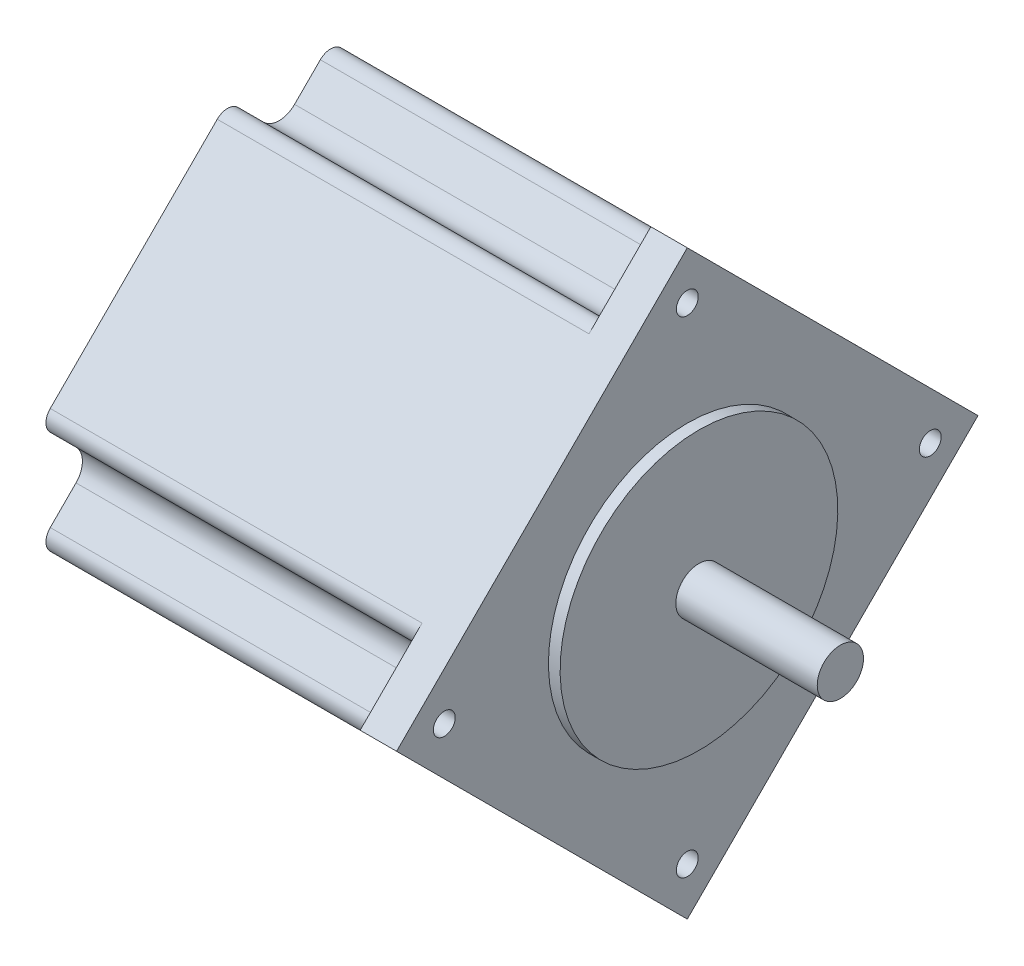
SolidWorks part; units mm, degrees
ref_plane "Plan de face" through (0, 0, 0) normal (0, 0, 1) x (1, 0, 0)
ref_plane "Plan de dessus" through (0, 0, 0) normal (0, 1, 0) x (1, 0, 0)
ref_plane "Plan de droite" through (0, 0, 0) normal (1, 0, 0) x (0, 0, -1)
ref_plane "Plan1" through (0, 607.4878, 607.4879) normal (0, 0.7071, 0.7071) x (-1, 0, 0)
sketch "Esquisse1" plane through (0, 607.4878, 607.4879) normal (0, 0.7071, 0.7071) x (-1, 0, 0)
  line L0 (138.3099, -364.0087) -> (138.3099, -307.6087)
  line L1 (138.3099, -307.6087) -> (82.3099, -307.6087)
  line L2 (82.3099, -307.6087) -> (82.3099, -364.0087)
  line L3 (82.3099, -364.0087) -> (138.3099, -364.0087)
  dimension "D1" = 56
  dimension "D2" = 56.4
extrude "Boss.-Extru.1" add sketch "Esquisse1" against normal blind 56.4
sketch "Esquisse2" plane through (0, 257.3931, -257.393) normal (0, 0.7071, -0.7071) x (-1, 0, 0)
  line L0 (138.31, 859.1175) -> (87.31, 859.1175)
  line L1 (87.31, 859.1175) -> (87.31, 849.1175)
  line L2 (87.31, 849.1175) -> (138.31, 849.1175)
  line L3 (138.31, 849.1175) -> (138.31, 859.1175)
  line L7 (82.31, 802.7175) -> (82.31, 859.1175) construction
  dimension "D1" = 5
  dimension "D2" = 10
extrude "Enlèv. mat.-Extru.1" cut sketch "Esquisse2" against normal blind 10
sketch "Esquisse3" plane through (0, 607.4878, 607.4879) normal (0, 0.7071, 0.7071) x (1, 0, 0)
  line L0 (-87.31, 307.6087) -> (-87.31, 317.6087)
  line L1 (-87.31, 317.6087) -> (-138.31, 317.6087)
  line L2 (-138.31, 317.6087) -> (-138.31, 307.6087)
  line L3 (-138.31, 307.6087) -> (-87.31, 307.6087)
  line L4 (-82.31, 307.6087) -> (-82.31, 364.0087) construction
  dimension "D1" = 10
  dimension "D2" = 5
extrude "Enlèv. mat.-Extru.2" cut sketch "Esquisse3" against normal blind 10
sketch "Esquisse4" plane through (0, 217.5122, -217.5122) normal (0, -0.7071, 0.7071) x (1, 0, 0)
  line L0 (-138.31, 802.7175) -> (-87.31, 802.7175)
  line L1 (-87.31, 802.7175) -> (-87.31, 812.7175)
  line L2 (-87.31, 812.7175) -> (-138.31, 812.7175)
  line L3 (-138.31, 812.7175) -> (-138.31, 802.7175)
  line L4 (-82.31, 802.7175) -> (-82.31, 859.1175) construction
  dimension "D1" = 10
  dimension "D2" = 5
extrude "Enlèv. mat.-Extru.3" cut sketch "Esquisse4" against normal blind 10
sketch "Esquisse5" plane through (0, 257.3931, -257.393) normal (0, 0.7071, -0.7071) x (-1, 0, 0)
  line L0 (87.31, 812.7175) -> (87.31, 802.7175)
  line L1 (87.31, 802.7175) -> (138.31, 802.7175)
  line L2 (138.31, 802.7175) -> (138.31, 812.7175)
  line L3 (138.31, 812.7175) -> (87.31, 812.7175)
  line L4 (82.31, 802.7175) -> (82.31, 859.1175) construction
  dimension "D1" = 10
  dimension "D2" = 5
extrude "Enlèv. mat.-Extru.4" cut sketch "Esquisse5" against normal blind 10
ref_plane "Plan2" through (0, 0, 350.0949) normal (0, 0, -1) x (-1, 0, 0)
hole_wizard "Diamètre du perçage Ø3.0 (3)1" positions "Esquisse8" profile "Esquisse7" hole size "Ø3.0" standard "Ansi Metric"
sketch "Esquisse8" plane through (-82.3099, 0, 0) normal (1, 0, 0) x (0, 0, -1)
  point P0 (-350.0949, 858.333)
  point P1 (-383.4279, 825)
  point P2 (-350.0949, 791.667)
  point P3 (-316.7619, 825)
  dimension "D1" = 47.14
  dimension "D2" = 47.14
sketch "Esquisse7" plane through (-82.31, 858.333, 350.0949) normal (0, 0, 1) x (0, 1, 0)
  line L0 (0, 0) -> (0, 56)
  line L1 (0, 56) -> (1.5, 56)
  line L2 (1.5, 56) -> (1.5, 0)
  line L5 (1.5, 0) -> (0, 0)
  line L11 (0, -6.35) -> (0, 107.95) construction
  dimension "Diamètre du perçage jusqu'au prochain" = 3
  dimension "Profondeur du perçage jusqu'au prochain" = 56
fillet "Congé1" radius 2 8 edges at (-112.81, 857.8097, 357.166) (-112.81, 792.1902, 343.0238) (-112.81, 857.8097, 343.0238) (-112.81, 832.0711, 317.2852) (-112.81, 817.9289, 317.2852) (-112.81, 817.9289, 382.9047) (-112.81, 832.0711, 382.9047) (-112.81, 792.1902, 357.166) tangent propagation no
fillet "Congé2" radius 3 4 edges at (-112.81, 825, 324.3562) (-112.81, 799.2613, 350.0949) (-112.81, 850.7387, 350.0949) (-112.81, 825, 375.8336) tangent propagation no
sketch "Esquisse9" plane through (-82.3099, 0, 0) normal (1, 0, 0) x (0, 0, -1)
  line L0 (-330.1545, 805.0596) -> (-370.0353, 844.9404) construction
  line L1 (-350.0949, 785.1192) -> (-310.2141, 825) construction
  line L2 (-389.9757, 825) -> (-350.0949, 864.8808) construction
  circle A0 centre (-350.0949, 825) radius 19.05
  dimension "D1" = 38.1
extrude "Boss.-Extru.2" add sketch "Esquisse9" along normal blind 1.6
sketch "Esquisse10" plane through (-80.7099, 0, 0) normal (1, 0, 0) x (0, 0, -1)
  circle A0 centre (-350.0949, 825) radius 3.175
  dimension "D1" = 6.35
extrude "Boss.-Extru.3" add sketch "Esquisse10" along normal blind 19.4
